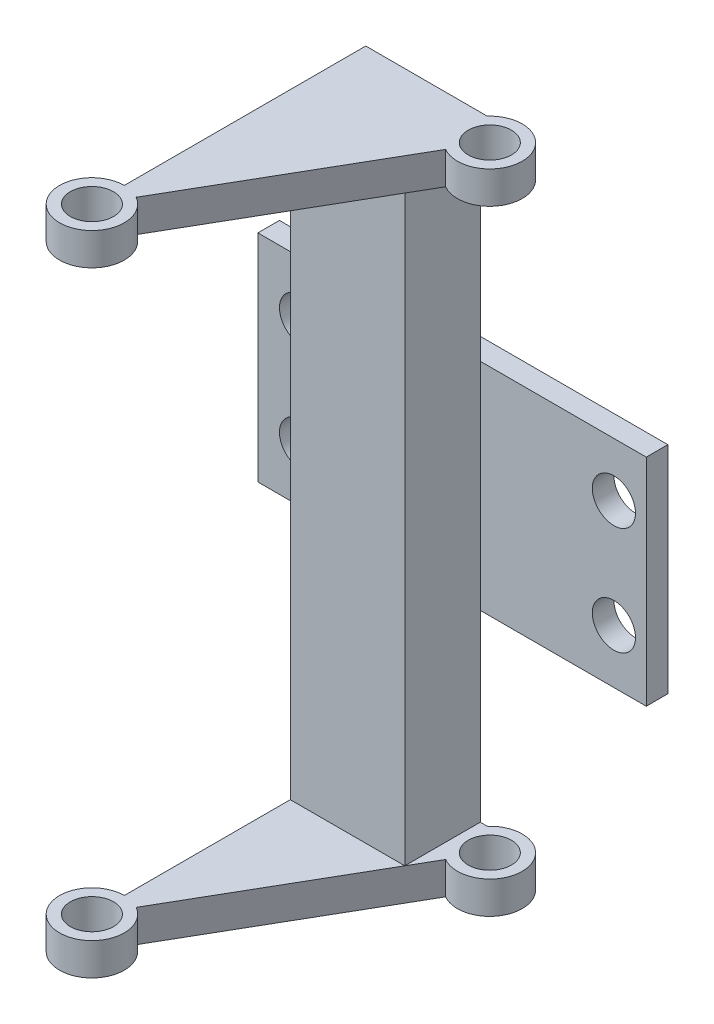
SolidWorks part; units mm, degrees
ref_plane "前视基准面" through (0, 0, 0) normal (0, 0, 1) x (1, 0, 0)
ref_plane "上视基准面" through (0, 0, 0) normal (0, 1, 0) x (1, 0, 0)
ref_plane "右视基准面" through (0, 0, 0) normal (1, 0, 0) x (0, 0, -1)
sketch "草图1" plane through (0, 0, 0) normal (0, 0, 1) x (1, 0, 0)
  line L3 (0, 0) -> (30, 0)
  line L4 (0, 0) -> (0, 20)
  line L5 (0, 20) -> (30, 20)
  line L6 (30, 0) -> (30, 20)
  circle A0 centre (4, 15) radius 2
  circle A1 centre (4, 5) radius 2
  dimension "D1" = 20
  dimension "D2" = 30
extrude "凸台-拉伸2" add sketch "草图1" along normal mid plane 2
sketch "草图2" plane through (0, 0, 0) normal (0, -1, 0) x (1, 0, 0)
  line L0 (10, 1) -> (21.2639, 1)
  line L1 (0, 1) -> (30, 1) construction
  line L4 (10, 3) -> (10, 1)
  line L5 (10, 3) -> (10, 23.3827)
  line L8 (11.5, 23.7846) -> (22, 5.5981)
  arc A0 (21.2639, 1) -> (22, 5.5981) centre (23.5, 3) ccw
  circle A1 centre (23.5, 3) radius 2
  circle A2 centre (10, 26.3827) radius 2
  arc A3 (11.5, 23.7846) -> (10, 23.3827) centre (10, 26.3827) ccw
  point P1 (0, 0)
  dimension "D1" = 27
sketch "草图3" plane through (30, 0, 0) normal (1, 0, 0) x (0, 0, -1)
  line L0 (16.7105, 0) -> (-16.7105, 0) construction
  line L1 (-1, 20) -> (1, 20)
  line L2 (-1, 20) -> (-1, 0)
  line L3 (-1, 0) -> (1, 0)
  line L4 (1, 20) -> (1, 0)
  line L5 (1, 0) -> (1, 20) construction
extrude "凸台-拉伸4" add sketch "草图3" along normal blind 6
sketch "草图4" plane through (0, 0, 1) normal (0, 0, 1) x (1, 0, 0)
  circle A0 centre (33, 15) radius 2
  circle A1 centre (33, 5) radius 2
extrude "切除-拉伸1" cut sketch "草图4" against normal blind 6
sketch "草图8" plane through (0, 0, 0) normal (0, 1, 0) x (1, 0, 0)
  line L0 (20.6143, -1) -> (20.6143, -7.9981)
  line L1 (11.5, -23.7846) -> (22, -5.5981) construction
  line L2 (20.6143, -7.9981) -> (10, -7.9981)
  line L3 (10, -3) -> (10, -23.3827) construction
  line L4 (10, -7.9981) -> (10, -1)
  line L5 (10, -1) -> (20.6143, -1)
  point P5 (21.2639, -6.873)
  point P11 (0, 0)
  point P12 (0, 0)
  point P13 (21.2639, -1)
  point P14 (0, 0)
  point P15 (0, 0)
  point P16 (20.6143, -7.9981)
extrude "凸台-拉伸6" add sketch "草图8" along normal blind 54 from offset 17 offset against normal yes
extrude "凸台-拉伸7" add sketch "草图2" along normal blind 3 from offset 17
extrude "凸台-拉伸8" add sketch "草图2<2>" against normal blind 3 from surface starting at face at (15.3072, 37, 4.4991)
sketch "草图2<2>" plane through (0, 0, 0) normal (0, -1, 0) x (1, 0, 0) same geometry as "草图2"
